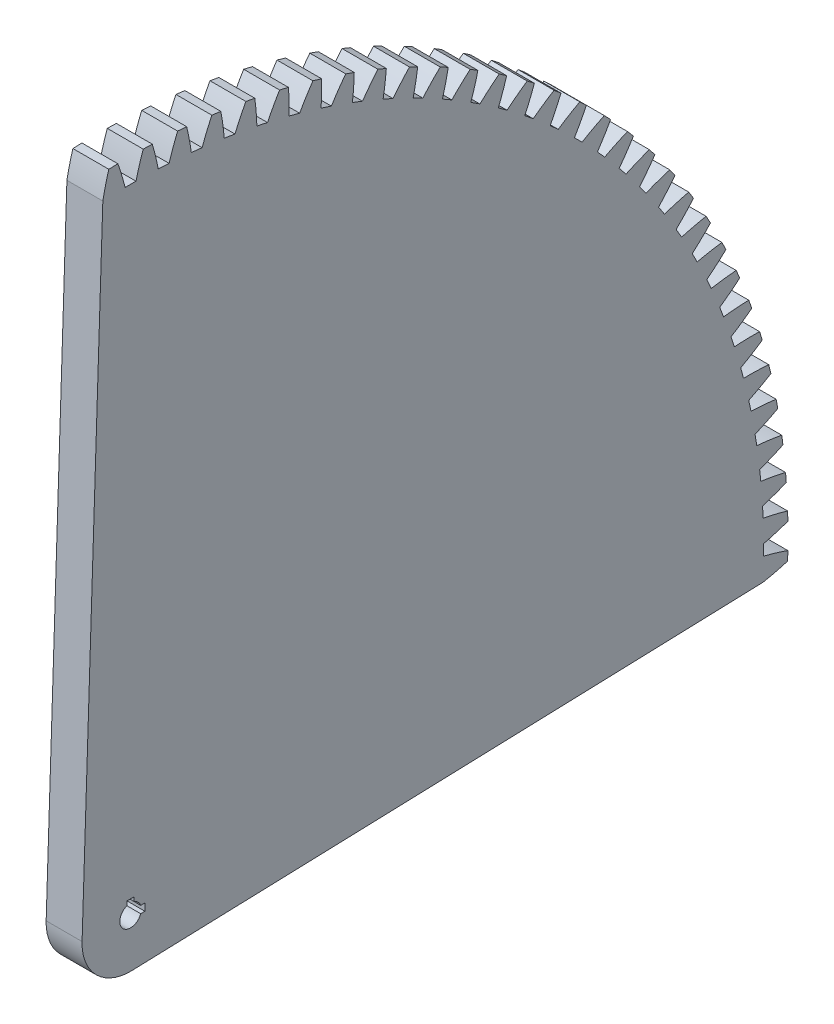
SolidWorks part; units mm, degrees
ref_plane "Plane1" through (0, 0, 0) normal (0, 0, 1) x (1, 0, 0)
ref_plane "Plane2" through (0, 0, 0) normal (0, 1, 0) x (1, 0, 0)
ref_plane "Plane3" through (0, 0, 0) normal (1, 0, 0) x (0, 0, -1)
sketch "HoldingSke" plane through (0, 0, 0) normal (0, 1, 0) x (1, 0, 0)
  line L0 (0, 0) -> (-0.1667, -0.2887)
  line L1 (-15, 0) -> (100, 0) construction
  line L2 (0, 0) -> (-2.1039, 2.3779)
  line L3 (0, 0) -> (-11.863, 4.5341)
  line L4 (0, 0) -> (-4.318, 7.479)
  line L5 (0, 0) -> (-46.8476, -17.4728)
  line L6 (0, 0) -> (-8.2896, -5.593)
  line L7 (-2.1039, 2.3779) -> (8.6586, 51.2059)
  line L8 (-76.2, 54.61) -> (-75.2, 54.61)
  line L9 (-67.7845, 28.3722) -> (-49.3413, 33.142)
  line L10 (-76.2, 71.12) -> (104.1128, 71.12)
  line L11 (0, 0) -> (-10, 0)
  line L12 (-76.2, 101.6) -> (-76.093, 101.6)
  line L13 (24.9733, 27.94) -> (52.9518, 28.4284)
  line L14 (24.9733, 27.94) -> (24.9743, 27.94)
  line L15 (24.9733, 27.94) -> (100.4006, 29.5858)
  line L16 (-63.627, -3) -> (-12.827, -3)
  circle A0 centre (0, 0) radius 3
  circle A1 centre (0, 0) radius 37.5
  circle A2 centre (0, 0) radius 37.5
  circle A3 centre (0, 0) radius 3
  dimension "MHD" = 75
  dimension "Hub_dia" = 75
  dimension "Bore" = 6
  dimension "MBD" = 6
  dimension "Num_teeth" = 120
  dimension "Pitch_radius" = 180.3128
  dimension "Pitch" = 0.3333
  dimension "Width" = 10
  dimension "Overall_len" = 50
  dimension "Show_teeth" = 120
  dimension "Thickness" = 10
  dimension "OAL" = 50.0001
  dimension "T_dim" = 1
  dimension "Ap" = 14.5
  dimension "H" = 19.05
  dimension "Backlash" = 0.107
  dimension "Addendum_fac" = 1
  dimension "Dedendum_fac" = 1.25
  dimension "Clearance_fac" = 0.25
  dimension "Dedendum_add" = 0.001
  dimension "Module" = 3
sketch "BasProSke" plane through (0, 0, 0) normal (0, 1, 0) x (1, 0, 0)
  line L0 (-10, 0) -> (60, 0) construction
  line L1 (0, 0) -> (0, 183)
  line L2 (0, 0) -> (10, 0)
  line L3 (10, 0) -> (10, 183)
  line L4 (10, 183) -> (0, 183)
  dimension "Diameter" = 366
  dimension "Thickness" = 10
revolve "Base-Revolve" add sketch "BasProSke" angle 360 about L0
sketch "TooCutSke" plane through (0, 0, 0) normal (1, 0, 0) x (0, 0, -1)
  line L1 (0, 0) -> (0, 107) construction
  line L2 (0, 0) -> (-2.5434, 179.982) construction
  line L3 (0, 0) -> (-9.423, 359.8505) construction
  line L4 (-2.5434, 179.982) -> (-4.7115, 179.9253) construction
  arc A0 (1.5113, 176.2425) -> (-1.5113, 176.2425) centre (0, 0) ccw
  arc A1 (3.5347, 182.9913) -> (-3.5347, 182.9913) centre (0, 0) ccw
  circle A2 centre (0, 0) radius 180 construction
  circle A3 centre (0, 0) radius 174.2666 construction
  arc A4 (-1.5113, 176.2425) -> (-3.5347, 182.9913) centre (-71.4076, 158.9648) ccw
  arc A5 (3.5347, 182.9913) -> (1.5113, 176.2425) centre (71.4076, 158.9648) ccw
  dimension "Root_dia" = 352.498
  dimension "Overcut_dia" = 366.0508
  dimension "Pitch_dia" = 360
  dimension "Base_dia" = 348.5332
  dimension "Flank_rad" = 72
  dimension "Half_ang" = 1.5
  dimension "Half_CT" = 2.1689
extrude "ToothCut" cut sketch "TooCutSke" along normal through all
fillet "Breaks" [suppressed] radius 0.06
fillet "RootFillets" [suppressed] radius 0.751
pattern_circular "TeethCuts" count 120 every 3 about axis through (-10, 0, 0) along (1, 0, 0) of "ToothCut", "RootFillets", "Breaks"
sketch "HubNeaOneSke" [suppressed] plane through (0, 0, 0) normal (-1, 0, 0) x (0, 0, 1)
  circle A0 centre (0, 0) radius 12.499
  dimension "Diameter" = 75
extrude "HubNearOne" [suppressed] add sketch "HubNeaOneSke" along normal blind 40.0001
sketch "HubNeaBotSke" [suppressed] plane through (0, 0, 0) normal (-1, 0, 0) x (0, 0, 1)
  circle A0 centre (0, 0) radius 12.7
  dimension "Diameter" = 75
extrude "HubNearBoth" [suppressed] add sketch "HubNeaBotSke" along normal blind 20
ref_plane "FarPln" through (10, 0, 0) normal (1, 0, 0) x (0, 0, -1)
sketch "HubFarSke" [suppressed] plane through (12.7, 0, 0) normal (1, 0, 0) x (0, 0, -1)
  circle A0 centre (0, 0) radius 12.7
  dimension "Diameter" = 75
extrude "HubFar" [suppressed] add sketch "HubFarSke" along normal blind 20
sketch "BorSke" plane through (0, 0, 0) normal (1, 0, 0) x (0, 0, -1)
  circle A0 centre (0, 0) radius 3
  dimension "Diameter" = 6
extrude "Bore" cut sketch "BorSke" along normal mid plane 100.0001
sketch "KeySke" plane through (0, 0, 0) normal (1, 0, 0) x (0, 0, -1)
  line L0 (-1, 0) -> (-1, 4)
  line L1 (-1, 4) -> (1, 4)
  line L2 (1, 4) -> (1, 0)
  line L3 (0, 0) -> (0, 34) construction
  line L4 (-1, 0) -> (1, 0)
  dimension "Offset" = 4
  dimension "Width" = 2
extrude "Keyway" cut sketch "KeySke" along normal mid plane 100.0001
pattern_circular "Keyway2" count 2 every 90 about axis through (0, 0, 0) along (1, 0, 0) of "Keyway"
sketch "Sketch1" plane through (10, 0, 0) normal (1, 0, 0) x (0, 0, -1)
  line L0 (0, 224.3134) -> (0, 0) construction
  line L1 (0, 0) -> (213.6921, 0) construction
  line L2 (176.0801, -7.7145) -> (0.4439, -13.4927)
  line L3 (-7.7145, 176.0801) -> (-13.4927, 0.4439)
  line L4 (176.0801, -7.7145) -> (186.3109, -8.4985)
  line L5 (186.3109, -8.4985) -> (187.8056, -54.5918)
  line L6 (187.8056, -54.5918) -> (141.6436, -161.7802)
  line L7 (141.6436, -161.7802) -> (0.4439, -208.078)
  line L8 (0.4439, -208.078) -> (-102.8323, -176.0574)
  line L9 (-102.8323, -176.0574) -> (-161.48, -112.2681)
  line L10 (-161.48, -112.2681) -> (-203.2321, -19.1491)
  line L11 (-203.2321, -19.1491) -> (-189.3957, 62.8481)
  line L12 (-189.3957, 62.8481) -> (-115.067, 184.8791)
  line L13 (-115.067, 184.8791) -> (-32.7498, 211.87)
  line L14 (-32.7498, 211.87) -> (-14.2518, 194.7007)
  line L15 (-14.2518, 194.7007) -> (-7.7145, 176.0801)
  arc A0 (-13.4927, 0.4439) -> (0.4439, -13.4927) centre (0, 0) ccw
  dimension "D1" = 27
extrude "Cut-Extrude1" cut sketch "Sketch1" against normal through all
equation "' \"Module@HoldingSke\" = 6.35"
equation "' \"Num_teeth@HoldingSke\" = 12"
equation "' \"Ap@HoldingSke\" =  20"
equation "' \"Width@HoldingSke\" = 0.5 * 25.4"
equation "' \"Hub_dia@HoldingSke\"= 1 * 25.4"
equation "' \"Overall_len@HoldingSke\" = 1.0 * 25.4"
equation "' \"Bore@HoldingSke\" = 0.75 * 25.4"
equation "' \"T_dim@HoldingSke\" = 0.1 * 25.4"
equation "' \"Width@KeySke\" = 0.25 * 25.4"
equation "' \"Show_teeth@HoldingSke\" = 13"
equation "' \"Backlash@HoldingSke\" = 0.009 * 25.4"
equation "' \"Addendum_fac@HoldingSke\" = 1.0"
equation "' \"Dedendum_fac@HoldingSke\" = 1.25"
equation "' \"Dedendum_add@HoldingSke\" = 0.00005 * 25.4"
equation "' \"Clearance_fac@HoldingSke\" = 0.25"
equation "\"Pitch@HoldingSke\" = 1 / \"Module@HoldingSke\""
equation "\"Overcut_dia@TooCutSke\" = (\"Num_teeth@HoldingSke\" + 2 * \"Addendum_fac@HoldingSke\") / \"Pitch@HoldingSke\" + 0.002 * 25.4"
equation "\"Pitch_dia@TooCutSke\" = \"Num_teeth@HoldingSke\" / \"Pitch@HoldingSke\""
equation "\"Base_dia@TooCutSke\" = \"Num_teeth@HoldingSke\" / \"Pitch@HoldingSke\" * cos((\"Ap@HoldingSke\"  * 3.14159265 / 180))"
equation "\"Root_dia@TooCutSke\" = (\"Num_teeth@HoldingSke\" + 2) / \"Pitch@HoldingSke\" - 2 * (\"Addendum_fac@HoldingSke\" + \"Dedendum_fac@HoldingSke\") / \"Pitch@HoldingSke\" - \"Dedendum_add@HoldingSke\" * 2"
equation "\"Half_ang@TooCutSke\" = 180 / \"Num_teeth@HoldingSke\""
equation "\"Half_CT@TooCutSke\" = \"Num_teeth@HoldingSke\" / \"Pitch@HoldingSke\" * sin((3.14159265 / 2 / \"Num_teeth@HoldingSke\")) / 2 - 7 * \"Backlash@HoldingSke\" / 4"
equation "\"Flank_rad@TooCutSke\" = \"Num_teeth@HoldingSke\" / \"Pitch@HoldingSke\" / 5"
equation "\"Radius@RootFillets\" = \"Clearance_fac@HoldingSke\" / \"Pitch@HoldingSke\" + \"Dedendum_add@HoldingSke\""
equation "\"Break_rad@Breaks\" = 0.02 / \"Pitch@HoldingSke\""
equation "\"Thickness@HoldingSke\" = \"Width@HoldingSke\""
equation "\"OAL@HoldingSke\" = \"Thickness@HoldingSke\""
equation "\"MHD@HoldingSke\" = (\"Num_teeth@HoldingSke\" + 2) / \"Pitch@HoldingSke\" - 2 * (\"Addendum_fac@HoldingSke\" + \"Dedendum_fac@HoldingSke\")  / \"Pitch@HoldingSke\" - \"Dedendum_add@HoldingSke\" * 2"
equation "\"MBD@HoldingSke\" = (\"Num_teeth@HoldingSke\" + 2) / \"Pitch@HoldingSke\" - 2 * (\"Addendum_fac@HoldingSke\" + \"Dedendum_fac@HoldingSke\")  / \"Pitch@HoldingSke\" - \"Dedendum_add@HoldingSke\" * 2 - 0.002 * 25.4"
equation "\"MHD@HoldingSke\" = ((sgn( \"MHD@HoldingSke\" - \"Hub_dia@HoldingSke\" )-1)*( \"MHD@HoldingSke\" - \"Hub_dia@HoldingSke\" ))/-2+ \"Hub_dia@HoldingSke\""
equation "\"MBD@HoldingSke\" = ((sgn( \"MBD@HoldingSke\" - \"Bore@HoldingSke\" )-1)*( \"MBD@HoldingSke\" - \"Bore@HoldingSke\" ))/-2+ \"Bore@HoldingSke\""
equation "\"OAL@HoldingSke\" = ((sgn( \"OAL@HoldingSke\" - \"Overall_len@HoldingSke\" )+1)*( \"OAL@HoldingSke\" - \"Overall_len@HoldingSke\" ))/2 + \"Overall_len@HoldingSke\" + 0.000002 * 25.4"
equation "\"Num_teeth@TeethCuts\" = int( \"Show_teeth@HoldingSke\" ) + 1"
equation "\"Num_teeth@TeethCuts\" = ((sgn( \"Num_teeth@TeethCuts\" - \"Num_teeth@HoldingSke\" )-1)*( \"Num_teeth@TeethCuts\" - \"Num_teeth@HoldingSke\" ))/-2+ \"Num_teeth@HoldingSke\""
equation "\"Num_teeth@TeethCuts\" = ((sgn( \"Num_teeth@TeethCuts\" - 2.0)+1)*( \"Num_teeth@TeethCuts\" - 2.0))/2 +2.0"
equation "\"Angle@TeethCuts\" = 360.0 / \"Num_teeth@HoldingSke\""
equation "\"Diameter@BasProSke\" = (\"Num_teeth@HoldingSke\" + 2 * \"Addendum_fac@HoldingSke\") / \"Pitch@HoldingSke\""
equation "\"Thickness@BasProSke\"  = \"Thickness@HoldingSke\""
equation "' \"Fillet_rad@BasProSke\" =  \"Thickness@HoldingSke\" * 0.05"
equation "\"MHD@HoldingSke\" = ((sgn( \"MHD@HoldingSke\" - \"Root_dia@TooCutSke\" )-1)*( \"MHD@HoldingSke\" - \"Root_dia@TooCutSke\" ))/-2+ \"Root_dia@TooCutSke\""
equation "\"Diameter@HubNeaOneSke\" = \"MHD@HoldingSke\""
equation "\"Length@HubNearOne\" = \"OAL@HoldingSke\" - \"Thickness@BasProSke\""
equation "\"Diameter@HubNeaBotSke\" = \"MHD@HoldingSke\""
equation "\"Length@HubNearBoth\" = ( \"OAL@HoldingSke\" - \"Thickness@BasProSke\" ) / 2.0"
equation "\"Thickness@FarPln\" = \"Thickness@BasProSke\""
equation "\"Diameter@HubFarSke\" = \"MHD@HoldingSke\""
equation "\"Length@HubFar\" = ( \"OAL@HoldingSke\" - \"Thickness@BasProSke\" ) / 2.0"
equation "\"Diameter@BorSke\" = \"MBD@HoldingSke\""
equation "\"D1@Bore\" = \"OAL@HoldingSke\" * 2.0"
equation "\"D1@Keyway\" = \"OAL@HoldingSke\" * 2.0"
equation "\"Offset@KeySke\" = \"T_dim@HoldingSke\" + \"MBD@HoldingSke\" / 2.0"
